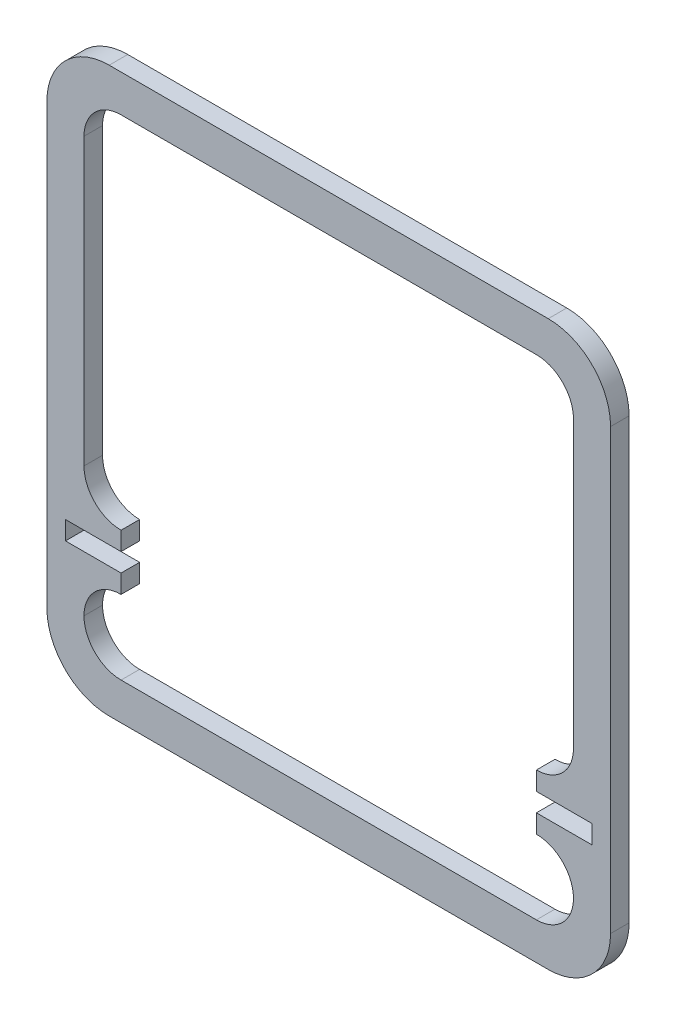
SolidWorks part; units mm, degrees
other "Markup1"
sketch "Sketch2" plane through (-48.26, -48.26, 3.175) normal (0, 0, 1) x (1, 0, 0)
other "Markup2"
sketch "Sketch3" plane through (48.26, 48.26, 3.175) normal (0.5188, 0.4948, 0.6971) x (0.8549, -0.3015, -0.4222)
material "Balsa"
ref_plane "Front Plane" through (0, 0, 0) normal (0, 0, 1) x (1, 0, 0)
ref_plane "Top Plane" through (0, 0, 0) normal (0, 1, 0) x (1, 0, 0)
ref_plane "Right Plane" through (0, 0, 0) normal (1, 0, 0) x (0, 0, -1)
sketch "Sketch1" plane through (0, 0, 0) normal (0, 0, 1) x (1, 0, 0)
  line L0 (-41.91, -41.91) -> (-41.91, -29.21)
  line L1 (-48.26, -48.26) -> (48.26, -48.26)
  line L2 (-48.26, -48.26) -> (-48.26, 48.26)
  line L3 (-48.26, 48.26) -> (48.26, 48.26)
  line L4 (48.26, -48.26) -> (48.26, 48.26)
  line L5 (0, 48.26) -> (0, -48.26) construction
  line L6 (-48.26, 0) -> (48.26, 0) construction
  line L11 (0, 12.156) -> (0, -12.156) construction
  line L12 (-19.2267, 0) -> (19.2267, 0) construction
  line L13 (-41.91, 41.91) -> (41.91, 41.91)
  line L14 (41.91, -41.91) -> (41.91, -29.21)
  line L15 (-41.91, -41.91) -> (41.91, -41.91)
  line L16 (-45.085, -26.035) -> (-35.56, -26.035)
  line L17 (-35.56, -26.035) -> (-35.56, -29.21)
  line L18 (-35.56, -29.21) -> (-41.91, -29.21)
  line L19 (-41.91, -19.685) -> (-35.56, -19.685)
  line L20 (-35.56, -19.685) -> (-35.56, -22.86)
  line L21 (-35.56, -22.86) -> (-45.085, -22.86)
  line L22 (-41.91, -19.685) -> (-41.91, 41.91)
  line L23 (-41.91, -41.91) -> (-41.91, 41.91) construction
  line L24 (-45.085, -26.035) -> (-45.085, -22.86)
  line L25 (35.56, -29.21) -> (41.91, -29.21)
  line L26 (35.56, -26.035) -> (35.56, -29.21)
  line L27 (45.085, -26.035) -> (35.56, -26.035)
  line L28 (45.085, -26.035) -> (45.085, -22.86)
  line L29 (35.56, -22.86) -> (45.085, -22.86)
  line L30 (35.56, -19.685) -> (35.56, -22.86)
  line L31 (41.91, -19.685) -> (35.56, -19.685)
  line L32 (41.91, -19.685) -> (41.91, 41.91)
  line L33 (41.91, -41.91) -> (41.91, 41.91) construction
  point P0 (0, 0)
  point P4 (0, 0)
  dimension "D1" = 96.52
  dimension "D2" = 96.52
  dimension "D4" = 3.175
  dimension "D5" = 3.175
  dimension "D6" = 12.7
  dimension "D7" = 6.35
  dimension "D3" = 6.35
extrude "Boss-Extrude1" add sketch "Sketch1" along normal blind 3.175
fillet "Fillet1" radius 10.668 4 edges at (48.26, -48.26, 1.5875) (48.26, 48.26, 1.5875) (-48.26, 48.26, 1.5875) (-48.26, -48.26, 1.5875)
fillet "Fillet2" radius 6.35 4 edges at (41.91, -41.91, 1.5875) (41.91, 41.91, 1.5875) (-41.91, 41.91, 1.5875) (-41.91, -41.91, 1.5875)
fillet "Fillet3" radius 6.35 4 edges at (41.91, -29.21, 1.5875) (41.91, -19.685, 1.5875) (-41.91, -19.685, 1.5875) (-41.91, -29.21, 1.5875)
